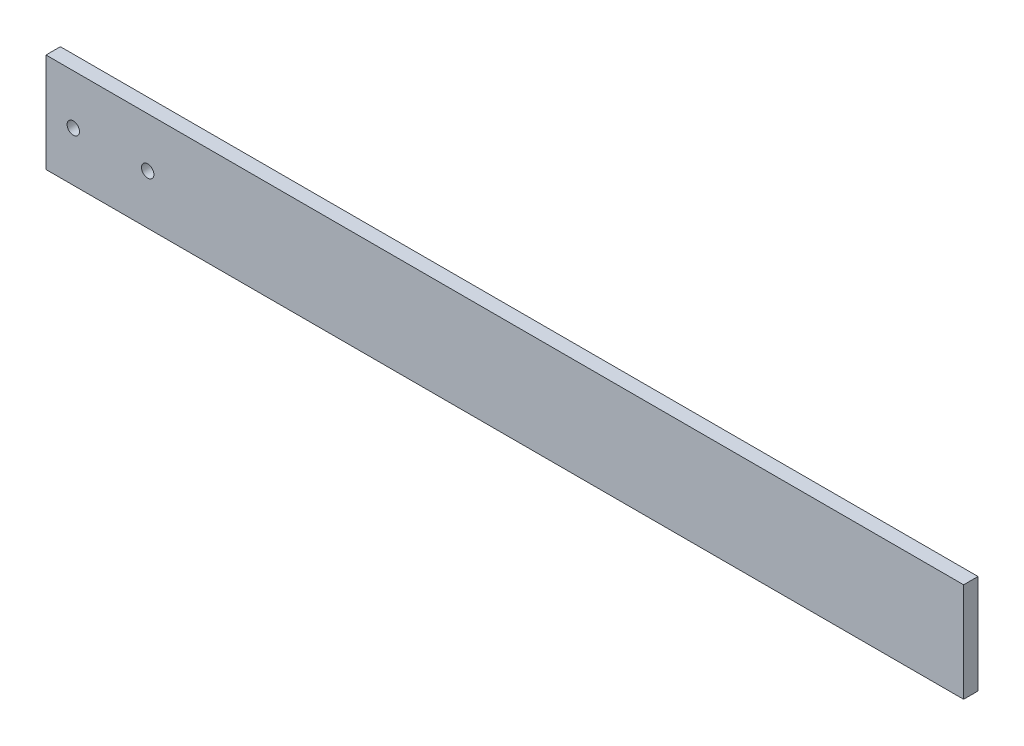
SolidWorks part; units mm, degrees
ref_plane "Front Plane" through (0, 0, 0) normal (0, 0, 1) x (1, 0, 0)
ref_plane "Top Plane" through (0, 0, 0) normal (0, 1, 0) x (1, 0, 0)
ref_plane "Right Plane" through (0, 0, 0) normal (1, 0, 0) x (0, 0, -1)
sketch "Sketch1" plane through (0, 0, 0) normal (0, 0, 1) x (1, 0, 0)
  line L1 (-92.5, 10) -> (92.5, 10)
  line L2 (-92.5, 10) -> (-92.5, -10)
  line L3 (-92.5, -10) -> (92.5, -10)
  line L4 (92.5, 10) -> (92.5, -10)
  line L5 (-92.5, 10) -> (92.5, -10) construction
  line L6 (-92.5, -10) -> (92.5, 10) construction
  point P0 (0, 0)
  dimension "D1" = 20
  dimension "D2" = 185
extrude "Boss-Extrude1" add sketch "Sketch1" against normal blind 2.9
sketch "Sketch2" plane through (0, 0, 0) normal (0, 0, 1) x (1, 0, 0)
  line L0 (-89.5, 10) -> (-89.5, -10) construction
  line L1 (92.5, 10) -> (-92.5, 10) construction
  line L2 (-92.5, -10) -> (92.5, -10) construction
  line L3 (-92.5, 10) -> (-92.5, -10) construction
  line L4 (-92.5, 0) -> (92.5, 0) construction
  line L5 (92.5, -10) -> (92.5, 10) construction
  line L6 (-79.5, 10) -> (-79.5, -10) construction
  circle A0 centre (-79.5, 0) radius 10
  circle A1 centre (-87, 0) radius 1.25
  circle A2 centre (-72, 0) radius 1.25
  dimension "D2" = 20
  dimension "D3" = 2.5
  dimension "D4" = 15
  dimension "D1" = 3
extrude "Cut-Extrude1" cut sketch "Sketch2" against normal up to next contours A1 | A2 region at (-87, 0, 0) region at (-72, 0, 0)
